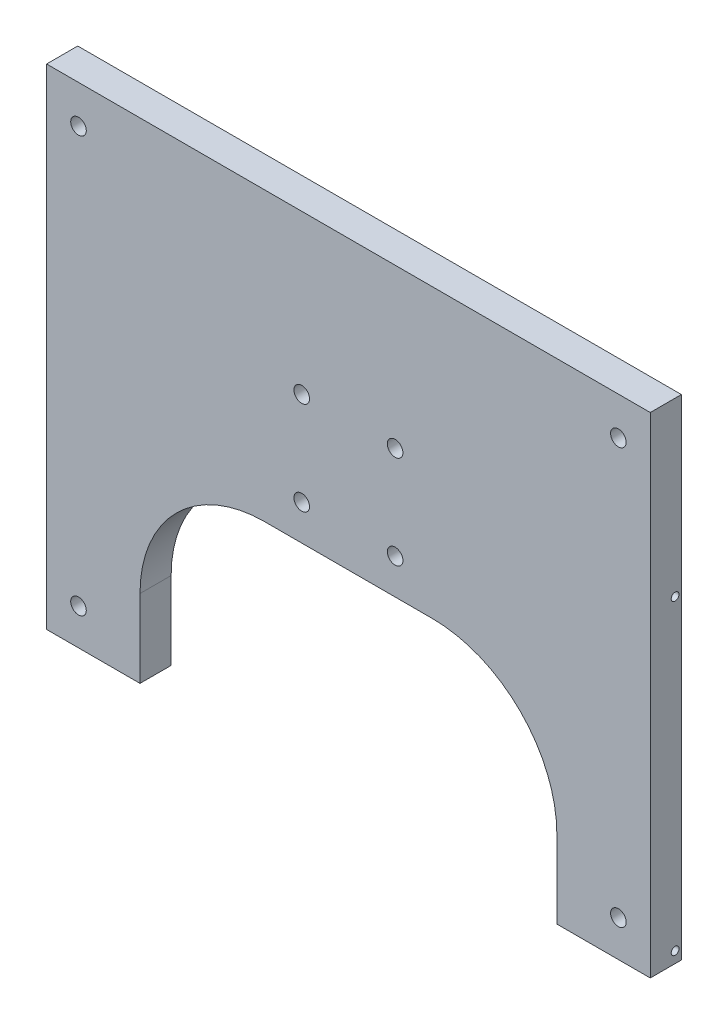
SolidWorks part; units mm, degrees
material "Beech"
ref_plane "Front Plane" through (0, 0, 0) normal (0, 0, 1) x (1, 0, 0)
ref_plane "Top Plane" through (0, 0, 0) normal (0, 1, 0) x (1, 0, 0)
ref_plane "Right Plane" through (0, 0, 0) normal (1, 0, 0) x (0, 0, -1)
sketch "Sketch1" plane through (0, 0, 0) normal (0, 0, 1) x (1, 0, 0)
  line L0 (258.9335, 10.7139) -> (12.7, 10.7139)
  line L1 (135.8167, -73.0143) -> (135.8167, 40.1583) construction
  line L2 (12.7, 10.7139) -> (12.7, -189.0518)
  line L3 (12.7, -189.0518) -> (50.8, -189.0518)
  line L4 (50.8, -189.0518) -> (50.8, -106.5018)
  line L5 (50.8, -106.5018) -> (220.8335, -106.5018)
  line L6 (135.8167, -205.9834) -> (135.8167, -73.0143) construction
  line L7 (135.8167, -106.5018) -> (135.8167, 10.7139) construction
  line L8 (271.3655, 10.7139) -> (0, 10.7139) construction
  line L9 (12.7, -189.0518) -> (12.7, 10.2705) construction
  line L10 (220.8335, -189.0518) -> (220.8335, -106.5018)
  line L11 (258.9335, -189.0518) -> (220.8335, -189.0518)
  line L12 (258.9335, 10.7139) -> (258.9335, -189.0518)
  dimension "D1" = 38.1
  dimension "D2" = 82.55
extrude "Boss-Extrude1" add sketch "Sketch1" against normal blind 12.7
hole_wizard "1/4 (0.25) Diameter Hole1" positions "Sketch4" profile "Sketch5" hole size "1/4" standard "ANSI Inch" end condition through all
sketch "Sketch4" plane through (0, 0, -12.7) normal (0, 0, -1) x (-1, 0, 0)
  point P0 (-25.7062, -174.2334)
  point P6 (-116.7667, -92.0643)
  point P9 (-154.8667, -92.0643)
  point P12 (-245.9273, -174.2334)
  point P15 (-154.8667, -53.9643)
  point P18 (-245.9273, -4.748)
  point P21 (-116.7667, -53.9643)
  point P24 (-25.7062, -4.748)
sketch "Sketch5" plane through (25.7062, -174.2334, -12.7) normal (1, 0, 0) x (0, 1, 0)
  line L0 (0, 0) -> (0, 12.7)
  line L1 (0, 12.7) -> (3.175, 12.7)
  line L2 (3.175, 12.7) -> (3.175, 0)
  line L5 (3.175, 0) -> (0, 0)
  line L11 (0, -6.35) -> (0, 107.95) construction
  dimension "Thru Hole Dia." = 6.35
  dimension "Thru Hole Depth" = 12.7
fillet "Fillet2" radius 50.8 2 edges at (220.8335, -106.5018, -6.35) (50.8, -106.5018, -6.35)
hole_wizard "Hole1" positions "Sketch6" profile "Sketch7" legacy
sketch "Sketch6" plane through (0, 1029.7044, 390.609) normal (-1, 0, 0) x (0, -0.2641, -0.9645)
  point P29 (707.1666, 1065.2704)
  point P31 (674.128, 944.6031)
sketch "Sketch7" plane through (0, -184.498, -10.1379) normal (0, 1, 0) x (0, 0, 1)
  line L0 (0, 0) -> (0, 39.0539)
  line L1 (0, 39.0539) -> (1.5875, 38.1)
  line L2 (1.5875, 38.1) -> (1.5875, 4.0177)
  line L3 (1.5875, 4.0177) -> (5.08, 0)
  line L4 (5.08, 0) -> (0, 0)
  line L5 (0, -14.3089) -> (0, 102.4216) construction
  line L6 (0, 39.0539) -> (-1.5875, 38.1) construction
  line L7 (-1.5875, 4.0177) -> (-5.08, 0) construction
  dimension "Diameter" = 3.175
  dimension "Depth" = 38.1
  dimension "C-Sink Diameter" = 10.16
  dimension "C-Sink Angle" = 82
  dimension "Drill Angle" = 118
ref_plane "Plane1" through (135.8167, 0, 0) normal (-1, 0, 0) x (0, 0, 1)
mirror "Mirror1" about plane through (135.8167, 0, 0) normal (-1, 0, 0) of "Hole1"
